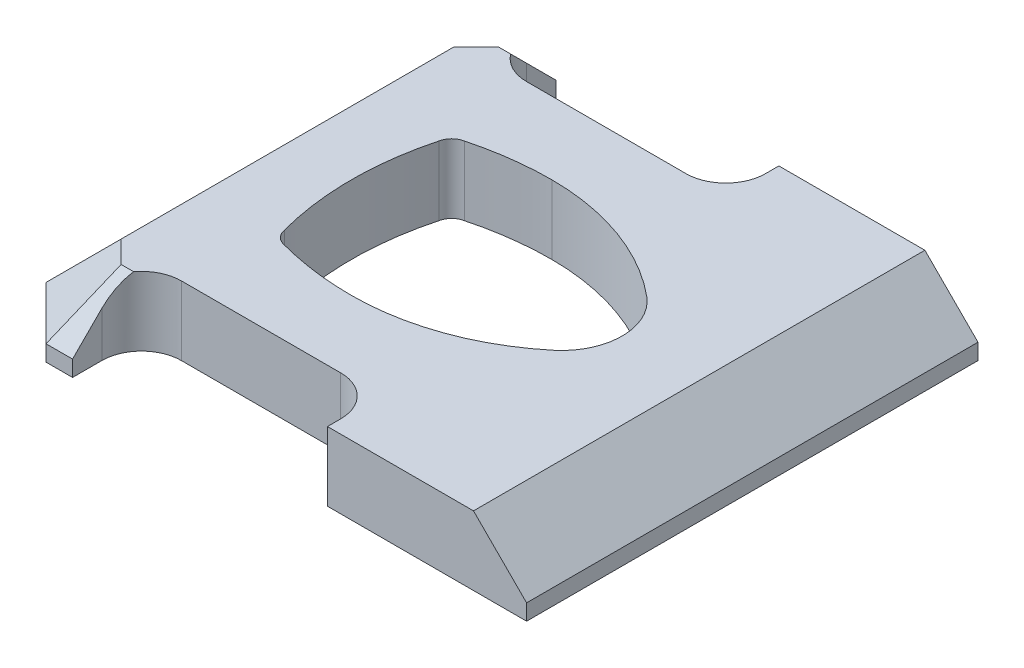
SolidWorks part; units mm, degrees
material "ABS"
ref_plane "Front Plane" through (0, 0, 0) normal (0, 0, 1) x (1, 0, 0)
ref_plane "Top Plane" through (0, 0, 0) normal (0, 1, 0) x (1, 0, 0)
ref_plane "Right Plane" through (0, 0, 0) normal (1, 0, 0) x (0, 0, -1)
sketch "Sketch1" plane through (0, 0, 0) normal (0, 1, 0) x (1, 0, 0)
  line L1 (-97.5, 85) -> (97.5, 85)
  line L2 (-97.5, 85) -> (-97.5, -85)
  line L3 (-97.5, -85) -> (97.5, -85)
  line L4 (97.5, 85) -> (97.5, -85)
  line L5 (-97.5, 85) -> (97.5, -85) construction
  line L6 (-97.5, -85) -> (97.5, 85) construction
  point P0 (0, 0)
  dimension "D1" = 195
  dimension "D2" = 170
extrude "Boss-Extrude1" add sketch "Sketch1" along normal blind 26
sketch "Sketch2" plane through (0, 26, 0) normal (0, 1, 0) x (1, 0, 0)
  line L0 (-97.5, -85) -> (-67.5, -85) construction
  line L1 (-97.5, -85) -> (97.5, -85) construction
  line L2 (0, 0) -> (-97.5, 0) construction
  line L3 (-67.5, -85) -> (22.5, -85)
  line L4 (-67.5, -85) -> (-67.5, -65)
  line L5 (-67.5, -65) -> (22.5, -65)
  line L6 (22.5, -85) -> (22.5, -65)
  line L7 (-97.5, 85) -> (-97.5, -85) construction
  line L8 (-67.5, 65) -> (22.5, 65)
  line L9 (22.5, 85) -> (22.5, 65)
  line L10 (-67.5, 85) -> (22.5, 85)
  line L11 (-67.5, 85) -> (-67.5, 65)
  dimension "D1" = 30
  dimension "D2" = 90
  dimension "D3" = 20
extrude "Cut-Extrude1" cut sketch "Sketch2" against normal through all
fillet "Fillet1" radius 15 4 edges at (22.5, 13, -65) (-67.5, 13, -65) (-67.5, 13, 65) (22.5, 13, 65)
sketch "Sketch3" plane through (0, 26, 0) normal (0, 1, 0) x (1, 0, 0)
  line L0 (0, 0) -> (-97.5, 0) construction
  line L1 (-67.5, 85) -> (-97.5, 85)
  line L2 (-67.5, 85) -> (-67.5, 91)
  line L3 (-67.5, 91) -> (-97.5, 91)
  line L4 (-97.5, 85) -> (-97.5, 91)
  line L5 (-97.5, 85) -> (-97.5, -85) construction
  line L6 (-67.5, -91) -> (-97.5, -91)
  line L7 (-97.5, -85) -> (-97.5, -91)
  line L8 (-67.5, -85) -> (-97.5, -85)
  line L9 (-67.5, -85) -> (-67.5, -91)
  dimension "D1" = 6
extrude "Boss-Extrude2" add sketch "Sketch3" against normal up to surface (26 mm away) up to face at (-16.875, 0, 0)
chamfer "Chamfer1" distance 20 angle 45 2 edges at (-97.5, 13, 91) (-97.5, 13, -91)
chamfer "Chamfer2" distance 20 angle 45 5 edges at (-72.5, 26, 91) (-72.5, 26, -91) (-97.5, 26, 0) (-87.5, 26, 81) (-87.5, 26, -81)
chamfer "Chamfer3" distance 20 angle 45 1 edges at (97.5, 26, 0)
sketch "Sketch6" plane through (0, 0, 0) normal (0, -1, 0) x (1, 0, 0)
  line L0 (51.5, -75) -> (82.1667, -75) construction
  line L5 (143.5, -85) -> (51.5, -85) construction
  line L6 (143.5, -85) -> (143.5, -65) construction
  line L7 (143.5, -65) -> (51.5, -65) construction
  line L8 (51.5, -85) -> (51.5, -65) construction
  line L9 (82.1667, -75) -> (112.8333, -75) construction
  line L10 (112.8333, -75) -> (143.5, -75) construction
  line L11 (0, 0) -> (97.5, 0) construction
  line L12 (97.5, 85) -> (97.5, -85) construction
  line L13 (97.5, -85) -> (22.5, -85) construction
  line L14 (-77.5, -91) -> (-67.5, -91) construction
  line L15 (-67.5, -91) -> (-67.5, -80) construction
  circle A2 centre (82.1667, -75) radius 6.1
  circle A3 centre (82.1667, 75) radius 6.1
  circle A4 centre (-75.5, -79.6) radius 6.1
  circle A5 centre (-75.5, 79.6) radius 6.1
  point P6 (97.5, -75)
  dimension "D3" = 12.2
  dimension "D6" = 12.2
  dimension "D1" = 92
  dimension "D2" = 20
  dimension "D4" = 11.4
  dimension "D5" = 8
extrude "Cut-Extrude4" cut sketch "Sketch6" against normal blind 3.2
fillet "Fillet2" radius 0.2 4 edges at (-75.5, 0, 85.7) (-75.5, 0, -85.7) (82.1667, 0, -81.1) (82.1667, 0, 81.1)
sketch "Sketch4" plane through (-97.5, 0, 0) normal (-1, 0, 0) x (0, 0, 1)
  line L0 (-30.05, 16) -> (30.05, 16) construction
  line L1 (71, 6) -> (-71, 6) construction
  circle A0 centre (-30.05, 16) radius 7
  circle A1 centre (30.05, 16) radius 7
  point P4 (0, 16)
  dimension "D1" = 14
  dimension "D2" = 14
  dimension "D3" = 60.1
  dimension "D4" = 10
sketch "Sketch5" plane through (0, 0, 0) normal (0, -1, 0) x (1, 0, 0)
  line L0 (0, 0) -> (-97.5, 0) construction
  line L1 (-93.5, 37.55) -> (-77.5, 37.55)
  line L2 (-93.5, 37.55) -> (-93.5, 22.55) construction
  line L3 (-93.5, 22.55) -> (-77.5, 22.55)
  line L4 (-77.5, 37.55) -> (-77.5, 22.55) construction
  line L5 (-93.5, 37.55) -> (-77.5, 22.55) construction
  line L6 (-93.5, 22.55) -> (-77.5, 37.55) construction
  line L7 (-93.5, -22.55) -> (-77.5, -22.55)
  line L8 (-93.5, -22.55) -> (-93.5, -37.55) construction
  line L9 (-93.5, -37.55) -> (-77.5, -37.55)
  line L10 (-77.5, -22.55) -> (-77.5, -37.55) construction
  line L11 (-93.5, -22.55) -> (-77.5, -37.55) construction
  line L12 (-93.5, -37.55) -> (-77.5, -22.55) construction
  line L13 (-97.5, -71) -> (-97.5, 71) construction
  line L14 (-85.5, 30.05) -> (-85.5, -30.05) construction
  line L15 (-77.5, 37.55) -> (-62.5, 37.55) construction
  line L16 (-62.5, 37.55) -> (-62.5, -37.55)
  line L17 (-62.5, -37.55) -> (-77.5, -37.55) construction
  line L18 (-77.5, 22.55) -> (-77.5, -22.55)
  line L20 (-77.5, -37.55) -> (-62.5, -37.55) construction
  line L21 (-77.5, -37.55) -> (-77.5, -47.55)
  line L22 (-77.5, -47.55) -> (-62.5, -47.55)
  line L23 (-62.5, -37.55) -> (-62.5, -47.55)
  line L24 (-77.5, 37.55) -> (-62.5, 37.55) construction
  line L25 (-77.5, 37.55) -> (-77.5, 47.55)
  line L26 (-77.5, 47.55) -> (-62.5, 47.55)
  line L27 (-62.5, 37.55) -> (-62.5, 47.55)
  line L28 (-93.5, 37.55) -> (-96.5, 37.55)
  line L29 (-93.5, 37.55) -> (-93.5, 22.55) construction
  line L30 (-93.5, 22.55) -> (-96.5, 22.55)
  line L31 (-96.5, 37.55) -> (-96.5, 22.55)
  line L32 (-93.5, -22.55) -> (-96.5, -22.55)
  line L33 (-93.5, -22.55) -> (-93.5, -37.55) construction
  line L34 (-93.5, -37.55) -> (-96.5, -37.55)
  line L35 (-96.5, -22.55) -> (-96.5, -37.55)
  point P0 (-85.5, 30.05)
  point P5 (-85.5, -30.05)
  point P17 (-85.5, 0)
  dimension "D1" = 15
  dimension "D2" = 16
  dimension "D3" = 15
  dimension "D4" = 15
  dimension "D5" = 60.1
  dimension "D6" = 12
  dimension "D7" = 10
  dimension "D8" = 10
  dimension "D9" = 3
extrude "Cut-Extrude3" cut sketch "Sketch5" against normal blind 23
sketch "Sketch7" plane through (0, 0, 0) normal (0, -1, 0) x (1, 0, 0)
  line L0 (97.5, -85) -> (22.5, -85) construction
  line L1 (97.5, 85) -> (97.5, -85) construction
  line B0 (-50.4814, 0) -> (45.4814, 0) construction
  arc B1 (-44.5394, -30.8943) -> (-44.2077, -30.9649) centre (-43.75, -28) ccw construction
  arc B2 (-46.6443, -28.7894) -> (-44.5394, -30.8943) centre (-43.75, -28) ccw construction
  arc B3 (-46.7149, -28.4577) -> (-46.6443, -28.7894) centre (-43.75, -28) ccw construction
  arc B4 (-44.2077, 30.9649) -> (-44.5394, 30.8943) centre (-43.75, 28) ccw construction
  arc B5 (-44.5394, 30.8943) -> (-46.6443, 28.7894) centre (-43.75, 28) ccw construction
  arc B6 (-46.6443, 28.7894) -> (-46.7149, 28.4577) centre (-43.75, 28) ccw construction
  arc B7 (-46.7149, 28.4577) -> (-46.7149, -28.4577) centre (58.9083, 0) ccw construction
  arc B8 (-44.2077, -30.9649) -> (-15.75, -34.7314) centre (-15.75, 74.6583) ccw construction
  arc B9 (-15.75, -34.7314) -> (38.3655, -15.1715) centre (-15.75, 49.9083) ccw construction
  arc B10 (38.3655, -15.1715) -> (38.3655, 15.1715) centre (25.75, 0) ccw construction
  arc B11 (38.3655, 15.1715) -> (-15.75, 34.7314) centre (-15.75, -49.9083) ccw construction
  arc B12 (-15.75, 34.7314) -> (-44.2077, 30.9649) centre (-15.75, -74.6583) ccw construction
  arc B13 (-45.3288, -33.7886) -> (-44.855, -33.8974) centre (-43.75, -28) ccw
  arc B14 (-44.855, -33.8974) -> (-15.75, -37.7314) centre (-15.75, 74.6583) ccw
  arc B15 (-15.75, -37.7314) -> (40.2836, -17.4782) centre (-15.75, 49.9083) ccw
  arc B16 (40.2836, -17.4782) -> (40.2836, 17.4782) centre (25.75, 0) ccw
  arc B17 (40.2836, 17.4782) -> (-15.75, 37.7314) centre (-15.75, -49.9083) ccw
  arc B18 (-15.75, 37.7314) -> (-44.855, 33.8974) centre (-15.75, -74.6583) ccw
  arc B19 (-44.855, 33.8974) -> (-45.3288, 33.7886) centre (-43.75, 28) ccw
  arc B20 (-45.3288, 33.7886) -> (-49.5386, 29.5788) centre (-43.75, 28) ccw
  arc B21 (-49.5386, 29.5788) -> (-49.6474, 29.105) centre (-43.75, 28) ccw
  arc B22 (-49.6474, 29.105) -> (-49.6474, -29.105) centre (58.9083, 0) ccw
  arc B23 (-49.6474, -29.105) -> (-49.5386, -29.5788) centre (-43.75, -28) ccw
  arc B24 (-49.5386, -29.5788) -> (-45.3288, -33.7886) centre (-43.75, -28) ccw
  dimension "D1" = 85
  dimension "D2" = 100
sketch_block_instance "Block2-1"
sketch_block "Block2" parameters "D1"=3
extrude "Cut-Extrude5" cut sketch "Sketch7" against normal through all
sketch "Sketch8" plane through (0, 0, 0) normal (0, -1, 0) x (1, 0, 0)
  line L0 (-96.5, -37.55) -> (-77.5, -37.55) construction
  line L1 (-96.5, 37.55) -> (-91.5, 37.55)
  line L2 (-96.5, 37.55) -> (-96.5, -37.55)
  line L3 (-96.5, -37.55) -> (-91.5, -37.55)
  line L4 (-91.5, 37.55) -> (-91.5, -37.55)
  dimension "D1" = 5
extrude "Boss-Extrude3" add sketch "Sketch8" against normal up to vertex (7 mm away) up to point (-96.5, 7, -37.55)
